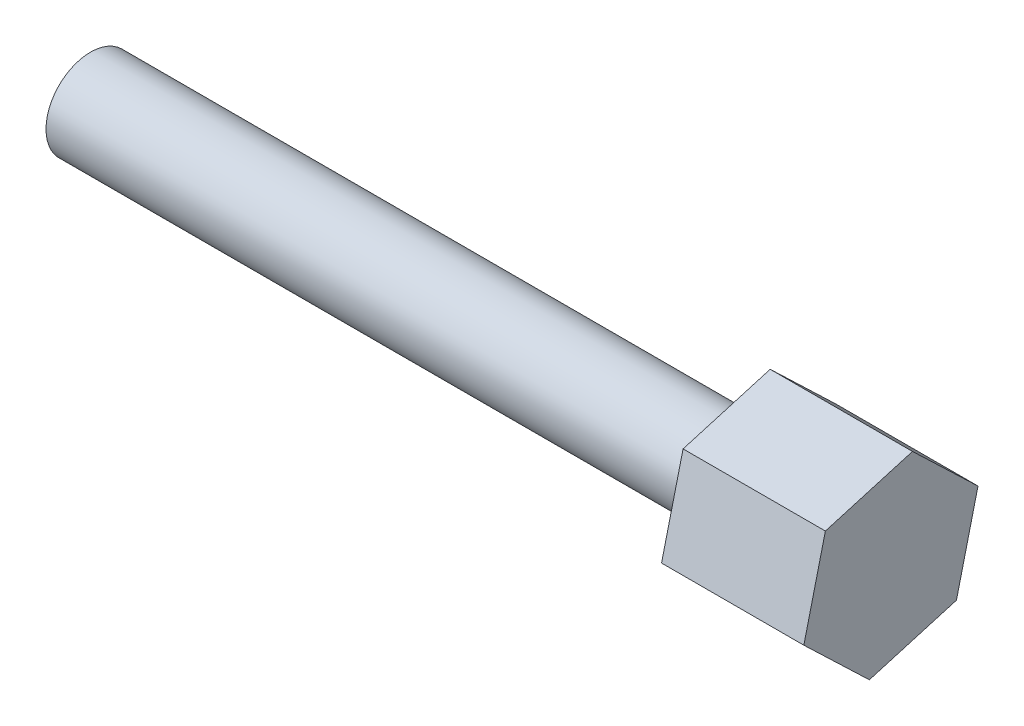
SolidWorks part; units mm, degrees
ref_plane "Front Plane" through (0, 0, 0) normal (0, 0, 1) x (1, 0, 0)
ref_plane "Top Plane" through (0, 0, 0) normal (0, 1, 0) x (1, 0, 0)
ref_plane "Right Plane" through (0, 0, 0) normal (1, 0, 0) x (0, 0, -1)
sketch "Sketch1" plane through (0, 0, 0) normal (1, 0, 0) x (0, 0, -1)
  circle A0 centre (0, 0) radius 3.175
extrude "Boss-Extrude2" add sketch "Sketch1" along normal blind 46.99 contours A0
sketch "Sketch2" plane through (46.99, 0, 0) normal (1, 0, 0) x (0, 0, -1)
  line L1 (-4.6788, 4.4782) -> (-6.2176, -1.8129)
  line L2 (-6.2176, -1.8129) -> (-1.5388, -6.2911)
  line L3 (-1.5388, -6.2911) -> (4.6788, -4.4782)
  line L4 (4.6788, -4.4782) -> (6.2176, 1.8129)
  line L5 (6.2176, 1.8129) -> (1.5388, 6.2911)
  line L6 (1.5388, 6.2911) -> (-4.6788, 4.4782)
  circle A0 centre (0, 0) radius 5.6088 construction
extrude "Boss-Extrude3" add sketch "Sketch2" along normal blind 10.16
sketch "Sketch3" plane through (0, 0, 0) normal (-1, 0, 0) x (0, 0, 1)
  circle A0 centre (0, 0) radius 1.778
  circle A1 centre (0, 0) radius 3.175
extrude "Cut-Extrude1" cut sketch "Sketch3" against normal blind 19.05
sketch "Sketch6" plane through (0, 0, 0) normal (-1, 0, 0) x (0, 0, 1)
  circle A0 centre (0, 0) radius 3.175
extrude "Boss-Extrude5" add sketch "Sketch6" against normal blind 49.022
sketch "Sketch7" plane through (0, 0, 0) normal (-1, 0, 0) x (0, 0, 1)
  line L1 (-0.4893, 0.7146) -> (-0.8635, -0.0664)
  line L2 (-0.8635, -0.0664) -> (-0.3742, -0.781)
  line L3 (-0.3742, -0.781) -> (0.4893, -0.7146)
  line L4 (0.4893, -0.7146) -> (0.8635, 0.0664)
  line L5 (0.8635, 0.0664) -> (0.3742, 0.781)
  line L6 (0.3742, 0.781) -> (-0.4893, 0.7146)
  circle A0 centre (0, 0) radius 0.75 construction
extrude "Cut-Extrude5" cut sketch "Sketch7" against normal blind 38.1
